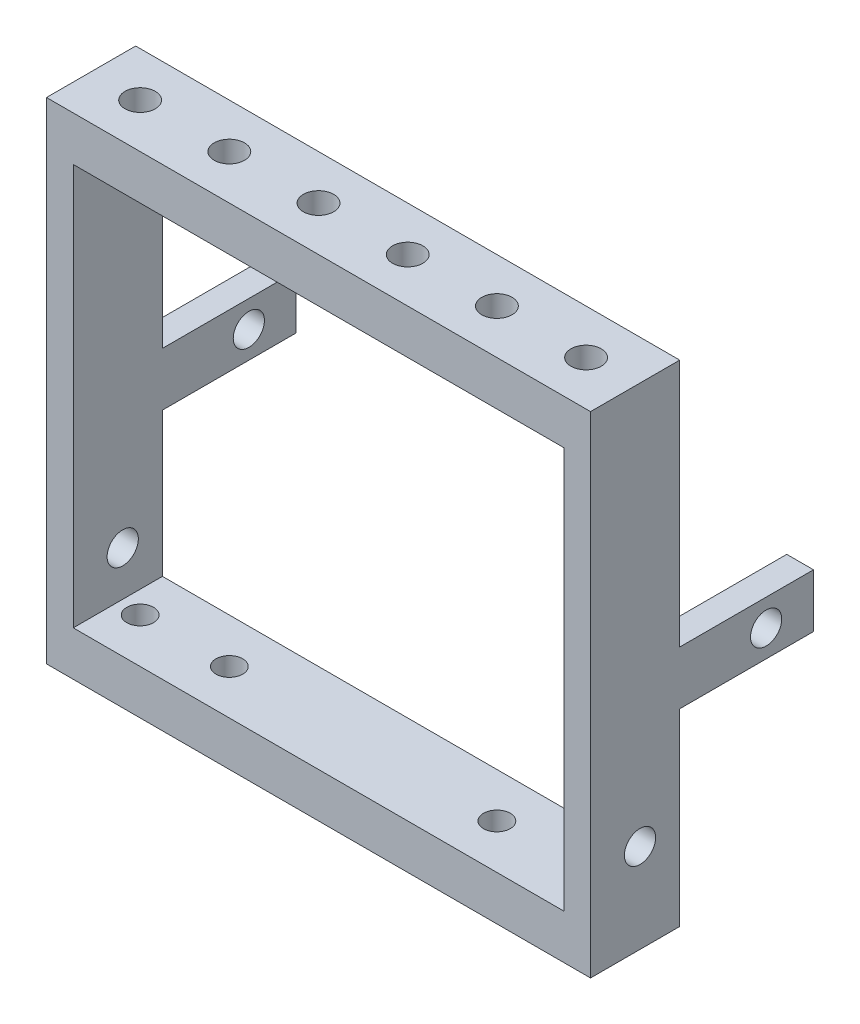
SolidWorks part; units mm, degrees
ref_plane "Front Plane" through (0, 0, 0) normal (0, 0, 1) x (1, 0, 0)
ref_plane "Top Plane" through (0, 0, 0) normal (0, 1, 0) x (1, 0, 0)
ref_plane "Right Plane" through (0, 0, 0) normal (1, 0, 0) x (0, 0, -1)
sketch "Sketch1" plane through (0, 0, 0) normal (0, 1, 0) x (1, 0, 0)
  line L1 (-23.3554, -4.3957) -> (37.6446, -4.3957)
  line L2 (-23.3554, -4.3957) -> (-23.3554, 5.6043)
  line L3 (-23.3554, 5.6043) -> (37.6446, 5.6043)
  line L4 (37.6446, -4.3957) -> (37.6446, 5.6043)
  circle A0 centre (-17.8554, 0.6043) radius 1.5
  circle A1 centre (-7.8554, 0.6043) radius 1.5
  circle A2 centre (22.1446, 0.6043) radius 1.5
  circle A3 centre (32.1446, 0.6043) radius 1.5
  dimension "D5" = 3
  dimension "D1" = 10
  dimension "D2" = 10
  dimension "D3" = 5.5
  dimension "D4" = 5.5
  dimension "D6" = 10
  dimension "D7" = 30
  dimension "D8" = 5
extrude "Boss-Extrude1" add sketch "Sketch1" along normal blind 5
sketch "Sketch2" plane through (0, 5, 0) normal (0, 1, 0) x (1, 0, 0)
  line L0 (37.6446, -4.3957) -> (37.6446, 5.6043) construction
  line L1 (-23.3554, -4.3957) -> (37.6446, -4.3957) construction
  line L2 (-23.3554, 5.6043) -> (-23.3554, -4.3957) construction
  line L3 (37.6446, 5.6043) -> (-23.3554, 5.6043) construction
  line L4 (37.6446, -4.3957) -> (37.6446, 5.6043)
  line L5 (-23.3554, -4.3957) -> (-20.3554, -4.3957)
  line L6 (-23.3554, 5.6043) -> (-23.3554, -4.3957)
  line L7 (37.6446, 5.6043) -> (34.6446, 5.6043)
  line L8 (-20.3554, 5.6043) -> (-20.3554, -4.3957)
  line L9 (34.6446, 5.6043) -> (34.6446, -4.3957)
  line L10 (-20.3554, 5.6043) -> (-23.3554, 5.6043)
  line L11 (34.6446, -4.3957) -> (37.6446, -4.3957)
  dimension "D1" = 3
  dimension "D2" = 3
extrude "Boss-Extrude2" add sketch "Sketch2" along normal blind 45
sketch "Sketch3" plane through (-23.3554, 0, 0) normal (-1, 0, 0) x (0, 0, 1)
  line L0 (-5.6043, 5) -> (4.3957, 5) construction
  line L1 (-5.6043, 5) -> (4.3957, 5) construction
  circle A0 centre (-1.1522, 10) radius 1.75
  dimension "D1" = 3.5
  dimension "D2" = 5
extrude "Cut-Extrude1" cut sketch "Sketch3" against normal through all contours A0
sketch "Sketch4" plane through (-23.3554, 0, 0) normal (-1, 0, 0) x (0, 0, 1)
  line L0 (-5.6043, 50) -> (-5.6043, 0) construction
  line L1 (-5.6043, 21.14) -> (-20.6043, 21.14)
  line L2 (-5.6043, 21.14) -> (-5.6043, 27.14)
  line L3 (-5.6043, 27.14) -> (-20.6043, 27.14)
  line L4 (-20.6043, 21.14) -> (-20.6043, 27.14)
  circle A0 centre (-15.2922, 24.14) radius 1.75
  circle A1 centre (-1.1522, 10) radius 1.75 construction
  dimension "D1" = 3.5
  dimension "D3" = 14.14
  dimension "D5" = 3
  dimension "D2" = 14.14
  dimension "D4" = 6
  dimension "D6" = 15
extrude "Boss-Extrude3" add sketch "Sketch4" against normal blind 3 contours L1 L4 L3 L2
ref_plane "Plane1" through (7.1446, 0, 0) normal (-1, 0, 0) x (0, 0, 1)
mirror "Mirror1" about plane through (7.1446, 0, 0) normal (-1, 0, 0) of "Boss-Extrude3"
sketch "Sketch5" plane through (-23.3554, 0, 0) normal (-1, 0, 0) x (0, 0, 1)
  circle A0 centre (-15.2922, 24.14) radius 1.75
  circle A1 centre (-1.1522, 10) radius 1.75 construction
  dimension "D1" = 3.5
  dimension "D2" = 14.14
  dimension "D3" = 14.14
extrude "Cut-Extrude2" cut sketch "Sketch5" against normal through all
sketch "Sketch6" plane through (0, 50, 0) normal (0, 1, 0) x (1, 0, 0)
  line L0 (7.1446, 13.75) -> (7.1446, -13.75) construction
  line L1 (-23.3554, -4.3957) -> (37.6446, -4.3957)
  line L2 (-23.3554, -4.3957) -> (-23.3554, 5.6043)
  line L3 (-23.3554, 5.6043) -> (37.6446, 5.6043)
  line L4 (37.6446, -4.3957) -> (37.6446, 5.6043)
  circle A0 centre (2.1446, 0.6043) radius 1.7
  circle A1 centre (12.1446, 0.6043) radius 1.7
  circle A2 centre (-7.8554, 0.6043) radius 1.7
  circle A3 centre (-17.8554, 0.6043) radius 1.7
  circle A4 centre (22.1446, 0.6043) radius 1.7
  circle A5 centre (32.1446, 0.6043) radius 1.7
  dimension "D1" = 3.4
  dimension "D2" = 5
  dimension "D3" = 5
  dimension "D4" = 3
  dimension "D5" = 3
extrude "Boss-Extrude4" add sketch "Sketch6" along normal blind 5
